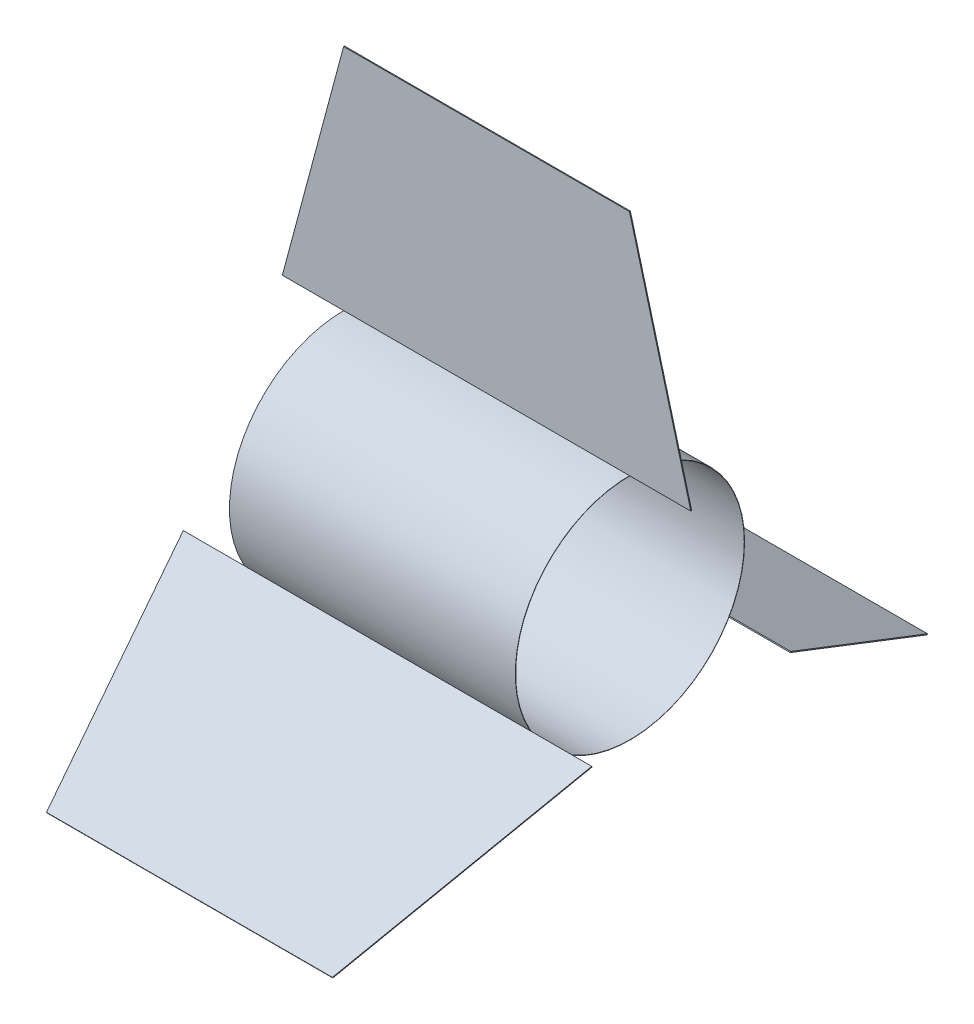
SolidWorks part; units mm, degrees
ref_plane "Front Plane" through (0, 0, 0) normal (0, 0, 1) x (1, 0, 0)
ref_plane "Top Plane" through (0, 0, 0) normal (0, 1, 0) x (1, 0, 0)
ref_plane "Right Plane" through (0, 0, 0) normal (1, 0, 0) x (0, 0, -1)
sketch "Sketch1" plane through (0, 0, 0) normal (1, 0, 0) x (0, 0, -1)
  circle A0 centre (0, 0) radius 101.6
  dimension "D1" = 203.2
extrude "Extrude-Thin1" add sketch "Sketch1" along normal blind 254 thin thin type one direction wall 0.254
sketch "Sketch2" plane through (0, 0, 0) normal (0, 0, 1) x (1, 0, 0)
  line L0 (308.4473, 101.854) -> (254, 305.054)
  line L1 (254, 305.054) -> (0, 305.054)
  line L2 (0, 305.054) -> (-54.4473, 101.854)
  line L3 (-54.4473, 101.854) -> (308.4473, 101.854)
  line L4 (127, 101.854) -> (127, -101.854) construction
  line L5 (0, -101.854) -> (254, -101.854) construction
  line L6 (254, 305.054) -> (254, 182.9577) construction
  dimension "D1" = 254
  dimension "D2" = 203.2
  dimension "D3" = 15
extrude "Boss-Extrude1" add sketch "Sketch2" along normal mid plane 0.7937 separate body
ref_axis "Axis1" through (-33.1969, 0, 0) along (1, 0, 0)
pattern_circular "CirPattern2" count 3 over 360 about axis through (-33.1969, 0, 0) along (1, 0, 0) of bodies 103
